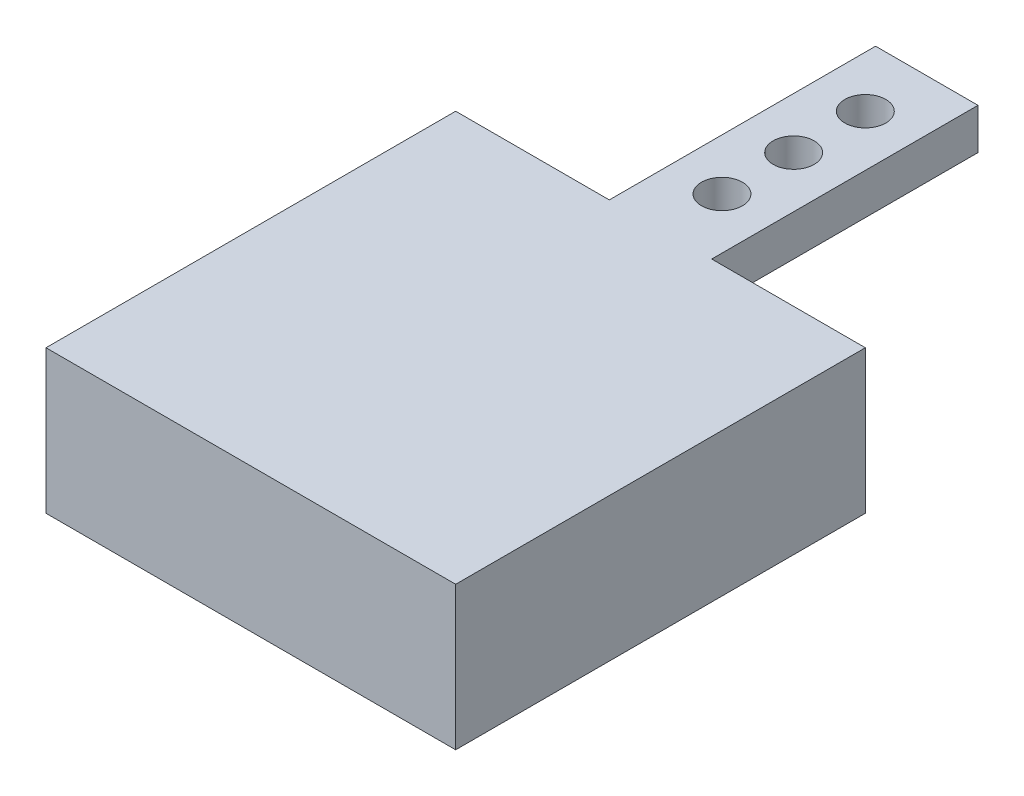
SolidWorks part; units mm, degrees
ref_plane "Front Plane" through (0, 0, 0) normal (0, 0, 1) x (1, 0, 0)
ref_plane "Top Plane" through (0, 0, 0) normal (0, 1, 0) x (1, 0, 0)
ref_plane "Right Plane" through (0, 0, 0) normal (1, 0, 0) x (0, 0, -1)
sketch "Sketch1" plane through (0, 0, 0) normal (0, 1, 0) x (1, 0, 0)
  line L1 (0, 0) -> (40, 0)
  line L2 (0, 0) -> (0, 40)
  line L3 (0, 40) -> (40, 40)
  line L4 (40, 0) -> (40, 40)
  dimension "D1" = 40
  dimension "D2" = 40
extrude "Boss-Extrude1" add sketch "Sketch1" along normal blind 14
sketch "Sketch4" plane through (0, 0, -40) normal (0, 0, -1) x (-1, 0, 0)
  line L1 (-20, 0) -> (-20, 14) construction
  line L2 (-40, 0) -> (0, 0) construction
  line L3 (-40, 14) -> (0, 14) construction
  line L5 (-15, 14) -> (-25, 14)
  line L6 (-15, 14) -> (-15, 10)
  line L7 (-15, 10) -> (-25, 10)
  line L8 (-25, 14) -> (-25, 10)
  point P10 (-20, 10)
  dimension "D1" = 4
  dimension "D2" = 10
extrude "Boss-Extrude3" add sketch "Sketch4" along normal blind 26
sketch "Sketch5" plane through (0, 14, 0) normal (0, 1, 0) x (1, 0, 0)
  line L0 (20, 66) -> (20, 0) construction
  line L1 (15, 66) -> (25, 66) construction
  line L2 (0, 0) -> (40, 0) construction
  circle A0 centre (20, 60) radius 2
  circle A1 centre (20, 53) radius 2
  circle A2 centre (20, 46) radius 2
  dimension "D2" = 4
  dimension "D3" = 4
  dimension "D4" = 4
  dimension "D1" = 6
  dimension "D5" = 7
  dimension "D6" = 7
extrude "Cut-Extrude2" cut sketch "Sketch5" against normal blind 26
